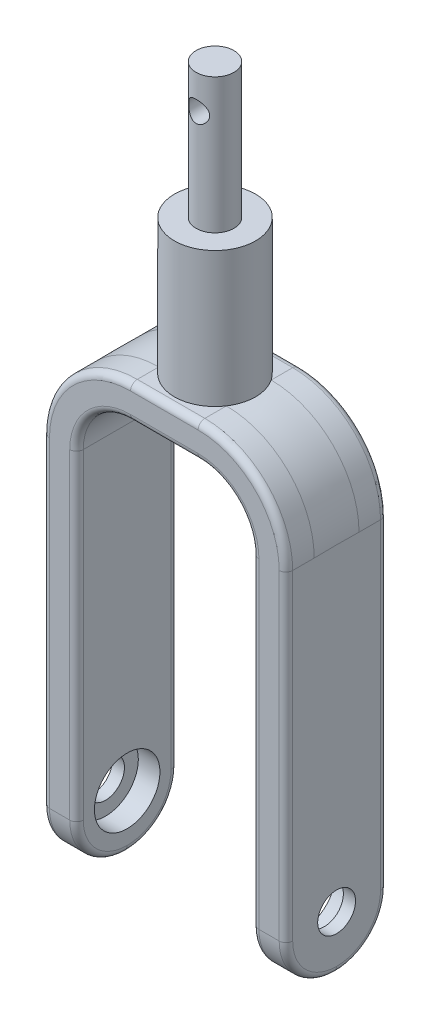
SolidWorks part; units mm, degrees
ref_plane "前视基准面" through (0, 0, 0) normal (0, 0, 1) x (1, 0, 0)
ref_plane "上视基准面" through (0, 0, 0) normal (0, 1, 0) x (1, 0, 0)
ref_plane "右视基准面" through (0, 0, 0) normal (1, 0, 0) x (0, 0, -1)
sketch "草图1" plane through (0, 0, 0) normal (0, 1, 0) x (1, 0, 0)
  line L1 (18, 7.5) -> (-18, 7.5)
  line L2 (18, 7.5) -> (18, -7.5)
  line L3 (18, -7.5) -> (-18, -7.5)
  line L4 (-18, 7.5) -> (-18, -7.5)
  line L5 (18, 7.5) -> (-18, -7.5) construction
  line L6 (18, -7.5) -> (-18, 7.5) construction
  point P0 (0, 0)
extrude "凸台-拉伸1" add sketch "草图1" against normal blind 68
sketch "草图2" plane through (0, 0, 0) normal (0, 1, 0) x (1, 0, 0)
  circle A0 centre (0, 0) radius 6
extrude "凸台-拉伸2" add sketch "草图2" along normal blind 20
sketch "草图7" plane through (0, 20, 0) normal (0, 1, 0) x (1, 0, 0)
  circle A0 centre (0, 0) radius 2.8
extrude "凸台-拉伸3" add sketch "草图7" along normal blind 20
sketch "草图8" plane through (0, 0, 0) normal (0, 0, 1) x (1, 0, 0)
  line L0 (0, 20) -> (0, 35) construction
  line L1 (6, 20) -> (-6, 20) construction
  circle A1 centre (0, 35) radius 1.55
extrude "切除-拉伸5" cut sketch "草图8" against normal through all both and the other way through all
sketch "草图3" plane through (0, 0, 7.5) normal (0, 0, 1) x (1, 0, 0)
  line L0 (-18, -68) -> (18, -68) construction
  line L1 (-13, -68) -> (13, -68)
  line L2 (-13, -68) -> (-13, -5)
  line L3 (-13, -5) -> (13, -5)
  line L4 (13, -68) -> (13, -5)
extrude "切除-拉伸1" cut sketch "草图3" against normal through all
fillet "圆角1" radius 8 2 edges at (13, -5, 0) (-13, -5, 0)
fillet "圆角5" radius 13 2 edges at (18, 0, 0) (-18, 0, 0)
fillet "圆角3" radius 7.5 4 edges at (15.5, -68, -7.5) (15.5, -68, 7.5) (-15.5, -68, -7.5) (-15.5, -68, 7.5)
fillet "圆角2" radius 1 28 edges at (-18, -36.75, -7.5) (0, 0, -7.5) (18, -36.75, -7.5) (18, -36.75, 7.5) (0, 0, 7.5) (-18, -36.75, 7.5) (-10.6569, -7.3431, 7.5) (0, -5, 7.5) (10.6569, -7.3431, 7.5) (13, -36.75, 7.5) (13, -36.75, -7.5) (10.6569, -7.3431, -7.5) (0, -5, -7.5) (-10.6569, -7.3431, -7.5) (-13, -36.75, -7.5) (-13, -36.75, 7.5) (13, -65.8033, 5.3033) (13, -65.8033, -5.3033) (-13, -65.8033, -5.3033) (-13, -65.8033, 5.3033) (-18, -65.8033, 5.3033) (-18, -65.8033, -5.3033) (18, -65.8033, -5.3033) (18, -65.8033, 5.3033) (-14.1924, -3.8076, -7.5) (14.1924, -3.8076, -7.5) (14.1924, -3.8076, 7.5) (-14.1924, -3.8076, 7.5)
sketch "草图4" plane through (18, 0, 0) normal (1, 0, 0) x (0, 0, -1)
  circle A0 centre (0, -60) radius 2.8
extrude "切除-拉伸2" cut sketch "草图4" against normal through all
sketch "草图6" plane through (13, 0, 0) normal (1, 0, 0) x (0, 0, -1)
  circle A0 centre (0, -60) radius 4.85
extrude "切除-拉伸4" cut sketch "草图6" along normal blind 3.2
mirror "镜向1" about plane through (0, 0, 0) normal (1, 0, 0) of "切除-拉伸4"
